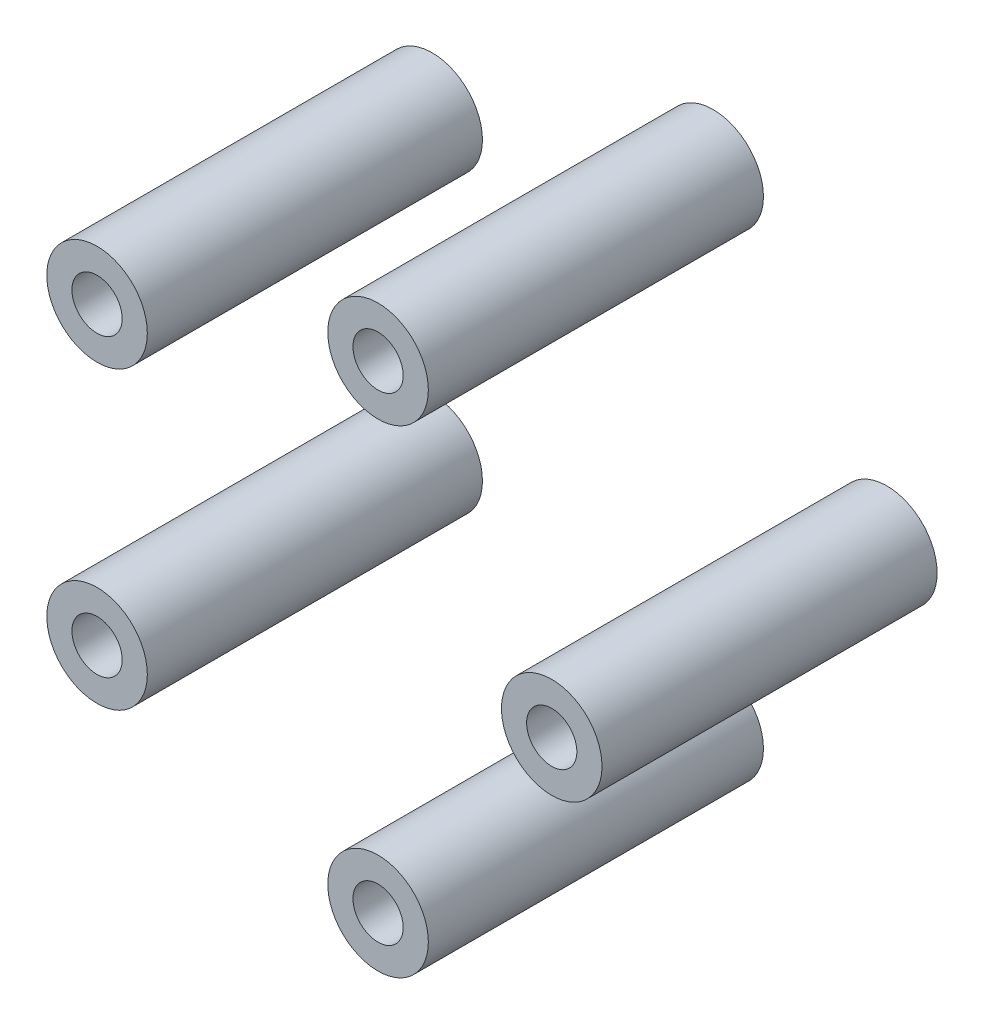
SolidWorks part; units mm, degrees
ref_plane "Front Plane" through (0, 0, 0) normal (0, 0, 1) x (1, 0, 0)
ref_plane "Top Plane" through (0, 0, 0) normal (0, 1, 0) x (1, 0, 0)
ref_plane "Right Plane" through (0, 0, 0) normal (1, 0, 0) x (0, 0, -1)
sketch "Sketch2" plane through (0, 0, -5.5) normal (0, 0, 1) x (1, 0, 0)
  line L0 (-16.6353, 8.8168) -> (-10.0353, 8.8168) construction
  line L1 (0.1353, 14.2658) -> (6.7353, 14.2658) construction
  line L2 (10.5, 0) -> (17.1, 0) construction
  line L3 (-16.6353, -8.8168) -> (-10.0353, -8.8168) construction
  line L4 (0.1353, -14.2658) -> (6.7353, -14.2658) construction
  circle A0 centre (-12.1353, 8.8168) radius 4.5 construction
  circle A1 centre (-14.5353, 8.8168) radius 4.5 construction
  circle A2 centre (4.6353, 14.2658) radius 4.5 construction
  circle A3 centre (2.2353, 14.2658) radius 4.5 construction
  circle A4 centre (15, 0) radius 4.5 construction
  circle A5 centre (12.6, 0) radius 4.5 construction
  circle A6 centre (-12.1353, -8.8168) radius 4.5 construction
  circle A7 centre (-14.5353, -8.8168) radius 4.5 construction
  circle A8 centre (4.6353, -14.2658) radius 4.5 construction
  circle A9 centre (2.2353, -14.2658) radius 4.5 construction
  circle A10 centre (-13.3353, 8.8168) radius 3
  circle A11 centre (-13.3353, 8.8168) radius 1.5
  circle A12 centre (3.4353, 14.2658) radius 3
  circle A13 centre (3.4353, 14.2658) radius 1.5
  circle A14 centre (13.8, 0) radius 3
  circle A15 centre (13.8, 0) radius 1.5
  circle A16 centre (3.4353, -14.2658) radius 3
  circle A17 centre (3.4353, -14.2658) radius 1.5
  circle A18 centre (-13.3353, -8.8168) radius 3
  circle A19 centre (-13.3353, -8.8168) radius 1.5
extrude "Boss-Extrude1" add sketch "Sketch2" along normal blind 12 and the other way blind 8
